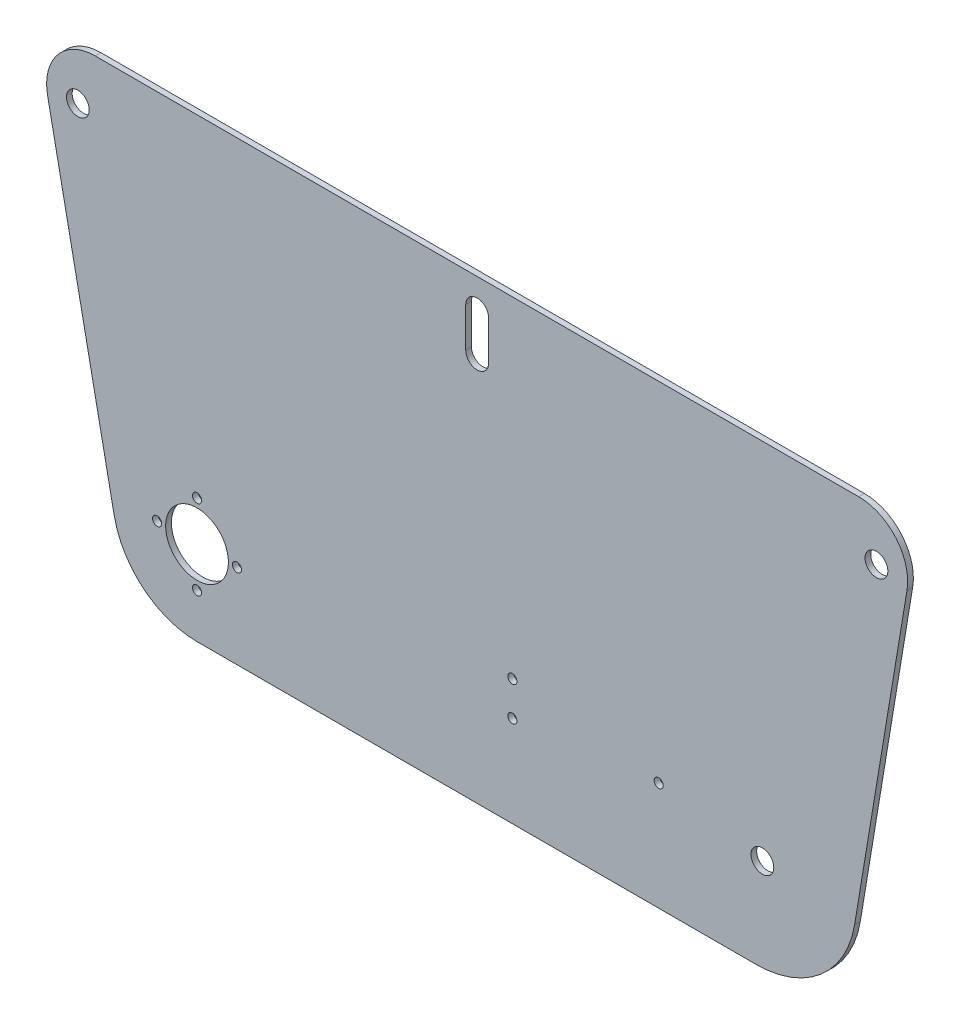
SolidWorks part; units mm, degrees
ref_plane "Front Plane" through (0, 0, 0) normal (0, 0, 1) x (1, 0, 0)
ref_plane "Top Plane" through (0, 0, 0) normal (0, 1, 0) x (1, 0, 0)
ref_plane "Right Plane" through (0, 0, 0) normal (1, 0, 0) x (0, 0, -1)
sketch "Sketch1" plane through (0, 0, 0) normal (0, 0, 1) x (1, 0, 0)
  line L1 (0, 0) -> (0, 115.062) construction
  line L2 (-140, 115.062) -> (140, 115.062) construction
  line L3 (-100, -37.4683) -> (100, -37.4683)
  line L4 (142.2945, 0.8576) -> (153.4347, 113.7361)
  line L5 (137.3964, 128.3085) -> (2.6036, 101.8154)
  line L6 (-2.6036, 101.8154) -> (-137.3964, 128.3085)
  line L7 (-153.3748, 113.2277) -> (-137.1523, -5.0634)
  line L8 (100, -34.9683) -> (-100, -34.9683) construction
  arc A12 (-137.1523, -5.0634) -> (-100, -37.4683) centre (-100, 0.0317) ccw
  arc A13 (100, -37.4683) -> (142.2945, 0.8576) centre (100, 5.0317) ccw
  arc A14 (153.4347, 113.7361) -> (137.3964, 128.3085) centre (140, 115.062) ccw
  arc A15 (2.6036, 101.8154) -> (-2.6036, 101.8154) centre (0, 115.062) cw
  arc A16 (-137.3964, 128.3085) -> (-153.3748, 113.2277) centre (-140, 115.062) ccw
  point P8 (0, 115.062)
  point P26 (0, -34.9683)
  circle B0 centre (-100, 0.0317) radius 35
  circle B1 centre (100, 5.0317) radius 40
  circle B2 centre (-140, 115.062) radius 11
  circle B3 centre (0, 115.062) radius 11
  circle B4 centre (140, 115.062) radius 11
  dimension "D1" = 200
  dimension "D3" = 280
  dimension "D7" = 279.5095
  dimension "D8" = 165.7768
sketch_block_instance "Block2-1"
sketch_block "Block2" parameters "D1"=52.784
sketch_block_instance "Block3-1"
sketch_block "Block3" parameters "D1"=49.6633
sketch_block_instance "Block4-1"
sketch_block "Block4"
sketch_block_instance "Block5-1"
sketch_block "Block5" parameters "D1"=22
sketch_block_instance "Block6-1"
sketch_block "Block6"
other "Belt1"
sketch "Sketch5" plane through (0, 0, 0) normal (0, 0, 1) x (1, 0, 0)
  line L12 (-100, -37.4683) -> (100, -37.4683) construction
  line L25 (110.1118, -2.4683) -> (77.5737, -2.4683)
  line L26 (65.3235, -2.4683) -> (34.5589, -2.4683)
  line L27 (134.4186, -22.4683) -> (143.6762, -22.4683)
  line L28 (143.4347, -2.4683) -> (134.6111, -2.4683)
  line L29 (143.4347, -2.4683) -> (143.4347, -22.4683)
  line L30 (16.6763, -22.4683) -> (134.2763, -22.4683)
  line L31 (15.513, -2.4683) -> (7.5179, -2.4683)
  line L32 (15.513, -22.4683) -> (7.5179, -22.4683)
  line L33 (7.5179, -2.4683) -> (7.5179, -22.4683)
  line L57 (14.6295, 0.5317) -> (66.6561, 0.5317)
  line L58 (66.6561, 0.5317) -> (66.6561, 7.0446)
  line L59 (66.6561, 14.0189) -> (66.6561, 20.5317)
  line L60 (66.6561, 20.5317) -> (14.6295, 20.5317)
  line L61 (10.0864, 20.5317) -> (8.6561, 20.5317)
  line L62 (8.6561, 20.5317) -> (8.6561, 19.2625)
  line L63 (8.6561, 13.801) -> (8.6561, 7.2625)
  line L64 (8.6561, 1.801) -> (8.6561, 0.5317)
  line L65 (8.6561, 0.5317) -> (10.0864, 0.5317)
  circle A0 centre (100, 5.0317) radius 11
  circle A2 centre (100, 5.0317) radius 7
  circle A29 centre (63.6561, 10.5317) radius 1.6
  circle A30 centre (12.3579, 16.5317) radius 1.6
  arc A36 (66.6561, 7.0446) -> (66.6561, 14.0189) centre (63.6561, 10.5317) ccw
  arc A37 (14.6295, 20.5317) -> (10.0864, 20.5317) centre (12.3579, 16.5317) ccw
  arc A38 (8.6561, 19.2625) -> (8.6561, 13.801) centre (12.3579, 16.5317) ccw
  arc A39 (8.6561, 7.2625) -> (8.6561, 1.801) centre (12.3579, 4.5317) ccw
  arc A40 (10.0864, 0.5317) -> (14.6295, 0.5317) centre (12.3579, 4.5317) ccw
  circle A41 centre (12.3579, 4.5317) radius 1.6
  point P4 (0, 0)
  dimension "D1" = 3.2
  dimension "D2" = 4.6
  dimension "D23" = 22
  dimension "D24" = 14
  dimension "D3" = 1.1383
  dimension "D4" = 2.5685
  dimension "D5" = 4.8401
  dimension "D6" = 136.1584
  dimension "D7" = 7.9951
  dimension "D8" = 9.1584
  dimension "D9" = 27.0411
  dimension "D10" = 56.1383
  dimension "D11" = 57.8057
  dimension "D12" = 59.1383
  dimension "D13" = 70.0559
  dimension "D14" = 102.594
  dimension "D15" = 126.7584
  dimension "D16" = 126.9007
  dimension "D17" = 127.0932
  dimension "D18" = 135.9169
  dimension "D19" = 20
  dimension "D20" = 23
  dimension "D21" = 29.5129
  dimension "D22" = 15
  dimension "D25" = 10
sketch "Sketch3" plane through (0, 0, 0) normal (0, 0, 1) x (1, 0, 0)
  line L0 (-98.2109, -27.4683) -> (97.7714, -27.4683)
  line L1 (-100, -37.4683) -> (100, -37.4683) construction
  line L2 (-127.245, -3.7047) -> (-150.6097, 112.1576)
  line L3 (132.3429, 1.8398) -> (150.7181, 112.5875)
  line L4 (-137.1523, -5.0634) -> (-127.245, -3.7047) construction
  line L5 (-153.3748, 113.2277) -> (-137.1523, -5.0634) construction
  line L6 (142.2945, 0.8576) -> (132.3429, 1.8398) construction
  line L7 (142.2945, 0.8576) -> (153.4347, 113.7361) construction
  line L8 (-133.934, 132.5317) -> (133.8103, 132.5317)
  line L9 (-4, 121.9902) -> (-4, 108.1338)
  line L10 (4, 121.9902) -> (4, 108.1338)
  circle A0 centre (-140, 115.062) radius 4
  circle A1 centre (0, 115.062) radius 4
  circle A2 centre (140, 115.062) radius 4
  circle A3 centre (100, 5.0317) radius 4
  circle A4 centre (-98.2109, 2.1503) radius 11
  circle A5 centre (-140, 115.062) radius 11 construction
  circle A6 centre (140, 115.062) radius 11 construction
  arc A7 (-98.2109, -27.4683) -> (-127.245, -3.7047) centre (-98.2109, 2.1503) cw
  arc A8 (97.7714, -27.4683) -> (132.3429, 1.8398) centre (97.7714, 7.5758) ccw
  arc A11 (150.7181, 112.5875) -> (133.8103, 132.5317) centre (133.8103, 115.3929) ccw
  arc A12 (-150.6097, 112.1576) -> (-133.934, 132.5317) centre (-133.934, 115.5204) cw
  circle A13 centre (63.6561, 10.5317) radius 1.6 construction
  circle A14 centre (12.3579, 4.5317) radius 1.6 construction
  circle A15 centre (12.3579, 16.5317) radius 1.6 construction
  circle A16 centre (63.6561, 10.5317) radius 1.6
  circle A17 centre (12.3579, 4.5317) radius 1.6
  circle A18 centre (12.3579, 16.5317) radius 1.6
  circle A19 centre (-98.2109, 2.1503) radius 14 construction
  circle A20 centre (-98.2109, 16.1503) radius 1.6
  circle A21 centre (-84.2109, 2.1503) radius 1.6
  circle A22 centre (-98.2109, -11.8497) radius 1.6
  circle A23 centre (-112.2109, 2.1503) radius 1.6
  circle A24 centre (0, 115.062) radius 8 construction
  arc A25 (-4, 121.9902) -> (4, 121.9902) centre (0, 121.9902) cw
  arc A26 (-4, 108.1338) -> (4, 108.1338) centre (0, 108.1338) ccw
  dimension "D1" = 8
  dimension "D5" = 22
  dimension "D6" = 28
  dimension "D7" = 3.2
  dimension "D2" = 10
  dimension "D3" = 10
  dimension "D4" = 160
  dimension "D9" = 8
  dimension "D8" = 4
extrude "Boss-Extrude1" add sketch "Sketch3" along normal blind 2 contours A12 L2 A7 L0 A8 L3 A11 L8 A26 L9 A25 L10 A23 A22 A21 A20 A18 A17 A16 A4 A3 A2 A0 region at (1.7014, 55.7712, 0)
